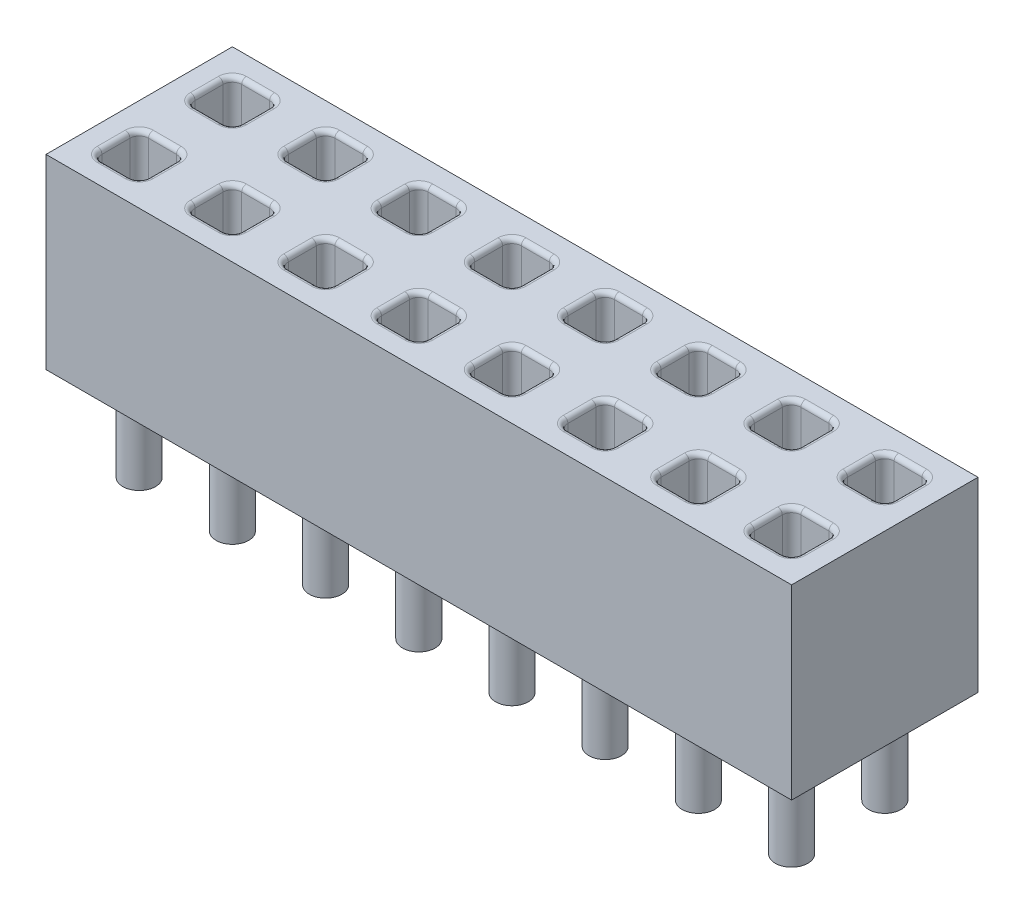
SolidWorks part; units mm, degrees
ref_plane "前视基准面" through (0, 0, 0) normal (0, 0, 1) x (1, 0, 0)
ref_plane "上视基准面" through (0, 0, 0) normal (0, 1, 0) x (1, 0, 0)
ref_plane "右视基准面" through (0, 0, 0) normal (1, 0, 0) x (0, 0, -1)
sketch "草图1" plane through (0, 0, 0) normal (0, 1, 0) x (1, 0, 0)
  line L1 (0, 0) -> (2, 0)
  line L2 (0, 0) -> (0, 2)
  line L3 (0, 2) -> (2, 2)
  line L4 (2, 0) -> (2, 2)
  dimension "D1" = 2
  dimension "D2" = 2
extrude "凸台-拉伸1" add sketch "草图1" along normal blind 4
sketch "草图2" plane through (0, 4, 0) normal (0, 1, 0) x (1, 0, 0)
  line L0 (1, 2) -> (1, 0) construction
  line L1 (2, 2) -> (0, 2) construction
  line L2 (0, 0) -> (2, 0) construction
  line L3 (0, 1) -> (2, 1) construction
  line L4 (0, 2) -> (0, 0) construction
  line L5 (2, 0) -> (2, 2) construction
  line L6 (0.7, 0.5) -> (1.3, 0.5)
  line L7 (0.7, 1.5) -> (1.3, 1.5)
  line L8 (0.5, 1.3) -> (0.5, 0.7)
  line L10 (1.5, 1.3) -> (1.5, 0.7)
  circle A0 centre (1, 1) radius 0.7 construction
  arc A1 (0.5, 0.7) -> (0.7, 0.5) centre (0.7, 0.7) ccw
  arc A2 (1.5, 0.7) -> (1.3, 0.5) centre (1.3, 0.7) cw
  arc A3 (1.5, 1.3) -> (1.3, 1.5) centre (1.3, 1.3) ccw
  arc A4 (0.7, 1.5) -> (0.5, 1.3) centre (0.7, 1.3) ccw
  point P18 (1.5, 1)
  point P20 (1, 0.5)
  point P21 (1, 1.5)
  point P23 (0.5, 0.5)
  point P26 (1.5, 0.5)
  point P29 (1.5, 1.5)
  point P32 (0.5, 1.5)
  dimension "D1" = 1.4
  dimension "D4" = 0.2
  dimension "D2" = 1
  dimension "D3" = 1
extrude "切除-拉伸1" cut sketch "草图2" against normal blind 3
sketch "草图3" plane through (0, 0, 0) normal (0, -1, 0) x (1, 0, 0)
  line L0 (1, -2) -> (1, 0) construction
  line L1 (2, -2) -> (0, -2) construction
  line L2 (0, 0) -> (2, 0) construction
  line L3 (0, -1) -> (2, -1) construction
  line L4 (0, -2) -> (0, 0) construction
  line L5 (2, 0) -> (2, -2) construction
  circle A0 centre (1, -1) radius 0.35
  dimension "D1" = 0.7
extrude "凸台-拉伸2" add sketch "草图3" along normal blind 2
pattern_linear "阵列(线性)1" count 8 spacing 2 along (1, 0, 0) count 2 spacing 2 along (0, 0, -1) of "凸台-拉伸2", "切除-拉伸1", "凸台-拉伸1"
fillet "圆角1" radius 0.1 128 edges at (1.4414, 4, -0.5586) (1, 4, -0.5) (0.5586, 4, -0.5586) (0.5, 4, -1) (0.5586, 4, -1.4414) (1, 4, -1.5) (1.4414, 4, -1.4414) (1.5, 4, -1) (13.4414, 4, -0.5586) (13, 4, -0.5) (12.5586, 4, -0.5586) (12.5, 4, -1) (12.5586, 4, -1.4414) (13, 4, -1.5) (13.4414, 4, -1.4414) (14.5586, 4, -0.5586) (14.5, 4, -1) (14.5586, 4, -1.4414) (15, 4, -1.5) (15.4414, 4, -1.4414) (15.5, 4, -1) (15.4414, 4, -0.5586) (10.5586, 4, -0.5586) (10.5, 4, -1) (10.5586, 4, -1.4414) (11, 4, -1.5) (11.4414, 4, -1.4414) (11.5, 4, -1) (11.4414, 4, -0.5586) (14.5586, 4, -2.5586) (14.5, 4, -3) (14.5586, 4, -3.4414) (15, 4, -3.5) (15.4414, 4, -3.4414) (15.5, 4, -3) (15.4414, 4, -2.5586) (12.5586, 4, -2.5586) (12.5, 4, -3) (12.5586, 4, -3.4414) (13, 4, -3.5) (13.4414, 4, -3.4414) (13.5, 4, -3) (13.4414, 4, -2.5586) (10.5586, 4, -2.5586) (10.5, 4, -3) (10.5586, 4, -3.4414) (11, 4, -3.5) (11.4414, 4, -3.4414) (11.5, 4, -3) (11.4414, 4, -2.5586) (9.4414, 4, -3.4414) (9.5, 4, -3) (9.4414, 4, -2.5586) (9, 4, -2.5) (8.5586, 4, -2.5586) (8.5, 4, -3) (8.5586, 4, -3.4414) (9.4414, 4, -1.4414) (9.5, 4, -1) (9.4414, 4, -0.5586) (9, 4, -0.5) (8.5586, 4, -0.5586) (8.5, 4, -1) (8.5586, 4, -1.4414) (7.4414, 4, -1.4414) (7.5, 4, -1) (7.4414, 4, -0.5586) (7, 4, -0.5) (6.5586, 4, -0.5586) (6.5, 4, -1) (6.5586, 4, -1.4414) (6.5586, 4, -2.5586) (6.5, 4, -3) (6.5586, 4, -3.4414) (7, 4, -3.5) (7.4414, 4, -3.4414) (7.5, 4, -3) (7.4414, 4, -2.5586) (4.5586, 4, -2.5586) (4.5, 4, -3) (4.5586, 4, -3.4414) (5, 4, -3.5) (5.4414, 4, -3.4414) (5.5, 4, -3) (5.4414, 4, -2.5586) (4.5586, 4, -0.5586) (4.5, 4, -1) (4.5586, 4, -1.4414) (5, 4, -1.5) (5.4414, 4, -1.4414) (5.5, 4, -1) (5.4414, 4, -0.5586) (2.5586, 4, -0.5586) (2.5, 4, -1) (2.5586, 4, -1.4414) (3, 4, -1.5) (3.4414, 4, -1.4414) (3.5, 4, -1) (3.4414, 4, -0.5586) (2.5586, 4, -3.4414) (3, 4, -3.5) (3.4414, 4, -3.4414) (3.5, 4, -3) (3.4414, 4, -2.5586) (3, 4, -2.5) (2.5586, 4, -2.5586) (0.5586, 4, -3.4414) (1, 4, -3.5) (1.4414, 4, -3.4414) (1.5, 4, -3) (1.4414, 4, -2.5586) (1, 4, -2.5) (0.5586, 4, -2.5586) (13.5, 4, -1) (15, 4, -0.5) (11, 4, -0.5) (15, 4, -2.5) (13, 4, -2.5) (11, 4, -2.5) (9, 4, -3.5) (9, 4, -1.5) (7, 4, -1.5) (7, 4, -2.5) (5, 4, -2.5) (5, 4, -0.5) (3, 4, -0.5) (2.5, 4, -3) (0.5, 4, -3)
